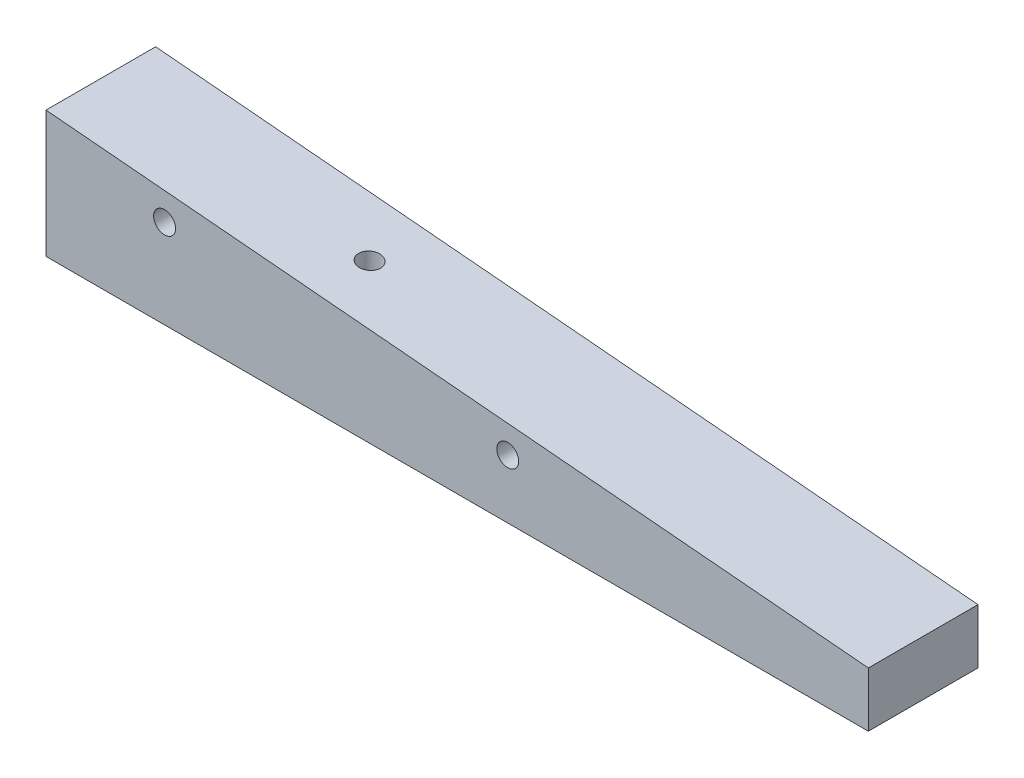
SolidWorks part; units mm, degrees
ref_plane "Front Plane" through (0, 0, 0) normal (0, 0, 1) x (1, 0, 0)
ref_plane "Top Plane" through (0, 0, 0) normal (0, 1, 0) x (1, 0, 0)
ref_plane "Right Plane" through (0, 0, 0) normal (1, 0, 0) x (0, 0, -1)
sketch "Sketch1" plane through (0, 0, 0) normal (0, 0, 1) x (1, 0, 0)
  line L2 (100.9722, 0) -> (-49.0278, 13.1233)
  line L5 (-49.0278, -10) -> (100.9722, -10)
  line L6 (100.9722, -10) -> (100.9722, 0)
  line L7 (-49.0278, 13.1233) -> (-49.0278, -10)
  dimension "D2" = 5
  dimension "D3" = 10
extrude "Boss-Extrude1" add sketch "Sketch1" along normal mid plane 20
sketch "Sketch2" plane through (0, -10, 0) normal (0, -1, 0) x (1, 0, 0)
  circle A0 centre (0, 0) radius 2
  dimension "D1" = 4
extrude "Cut-Extrude1" cut sketch "Sketch2" against normal through all
sketch "Sketch3" plane through (0, 0, 10) normal (0, 0, 1) x (1, 0, 0)
  line L0 (-26.9639, 11.193) -> (-27.3996, 6.212) construction
  line L2 (35.6299, 5.7167) -> (35.1941, 0.7357) construction
  line L3 (100.9722, 0) -> (-49.0278, 13.1233) construction
  circle A0 centre (-27.3996, 6.212) radius 2
  circle A1 centre (35.1941, 0.7357) radius 2
  dimension "D5" = 4
  dimension "D6" = 4
  dimension "D1" = 90
  dimension "D2" = 90
  dimension "D3" = 5
  dimension "D4" = 5
extrude "Cut-Extrude2" cut sketch "Sketch3" against normal through all both and the other way through all
